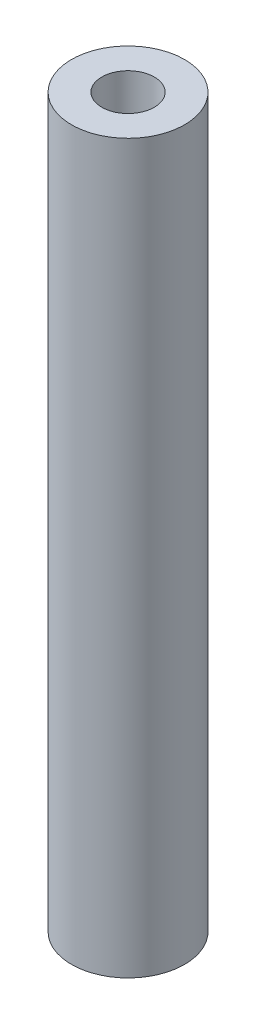
SolidWorks part; units mm, degrees
ref_plane "Front Plane" through (0, 0, 0) normal (0, 0, 1) x (1, 0, 0)
ref_plane "Top Plane" through (0, 0, 0) normal (0, 1, 0) x (1, 0, 0)
ref_plane "Right Plane" through (0, 0, 0) normal (1, 0, 0) x (0, 0, -1)
sketch "Sketch1" plane through (0, 0, 0) normal (0, 1, 0) x (1, 0, 0)
  circle A0 centre (0, 0) radius 7
  circle A1 centre (0, 0) radius 3.25
  dimension "D1" = 6.5
  dimension "D2" = 14
extrude "Boss-Extrude1" add sketch "Sketch1" along normal blind 90
